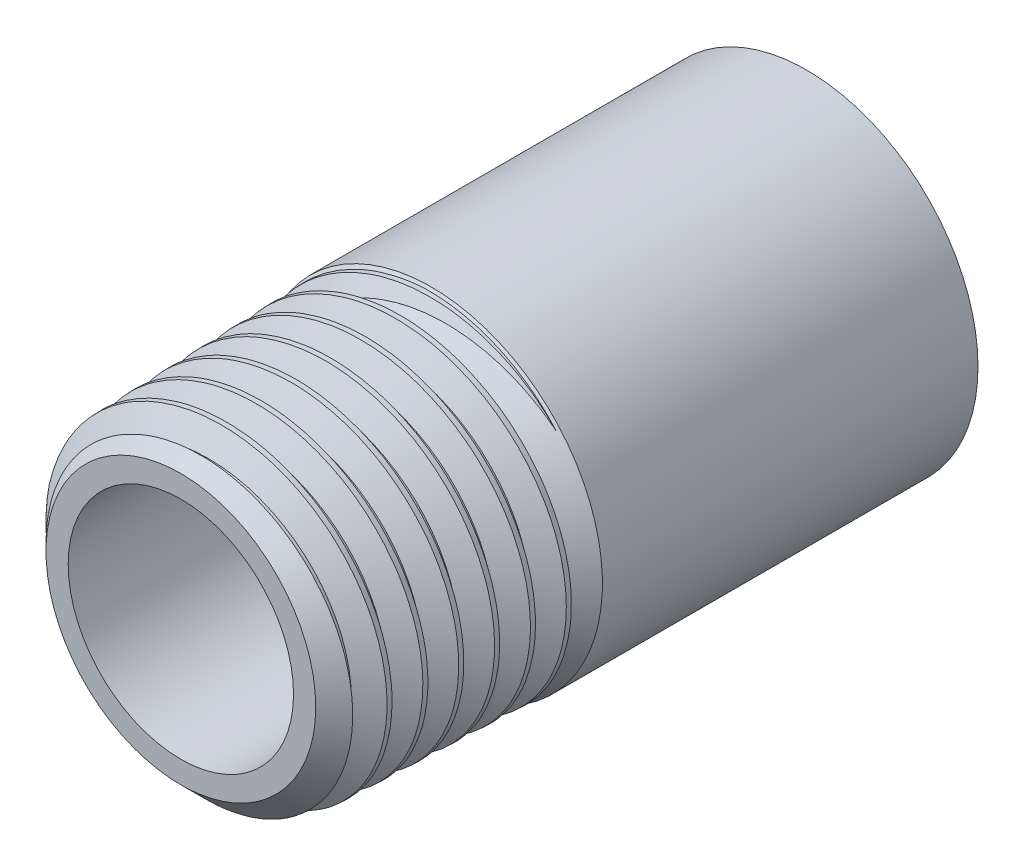
SolidWorks part; units mm, degrees
note: '?' marks a value the reader was unsure of.
ref_plane "Front" through (0, 0, 0) normal (0, 0, 1) x (1, 0, 0)
ref_plane "Top" through (0, 0, 0) normal (0, 1, 0) x (1, 0, 0)
ref_plane "Right" through (0, 0, 0) normal (1, 0, 0) x (0, 0, -1)
ref_axis "Axis1" through (0, 7.6398, 0) along (0, -1, 0)?
sketch "Layout" plane through (0, 0, 0) normal (1, 0, 0) x (0, 0, -1)
  line L0 (-12.7, 0) -> (12.7, 0) construction
  line L1 (-12.7, 4.572) -> (-12.7, 6.5417) construction
  line L2 (-12.7, 6.5417) -> (-2.54, 6.858) construction
  line L3 (-2.54, 6.858) -> (-2.54, 4.572) construction
  line L4 (-2.54, 4.572) -> (-12.7, 4.572) construction
  line L5 (0, 0) -> (0, 6.9453) construction
  point P9 (-2.54, 0)
  point P10 (-11.2889, 0)
  point P11 (2.54, 0)
  point P12 (11.2889, 0)
  dimension "D2" = 1.783
sketch "Sketch2" plane through (0, 0, 0) normal (1, 0, 0) x (0, 0, -1)
  line L0 (-12.7, 6.5417) -> (-2.54, 6.858) construction
  line L1 (-2.54, 6.858) -> (-2.54, 4.572) construction
  line L3 (-12.7, 4.572) -> (-12.7, 6.5417) construction
  line L4 (-12.7, 6.5417) -> (-2.54, 6.858)
  line L5 (-2.54, 6.858) -> (-2.54, 0)
  line L7 (-12.7, 0) -> (-12.7, 6.5417)
  line L8 (-12.7, 0) -> (-2.54, 0)
revolve "Revolve1" add sketch "Sketch2" angle 360 about L8
sketch "Sketch5" plane through (0, 0, 12.7) normal (0, 0, 1) x (1, 0, 0)
  circle A1 centre (0, 0) radius 6.5417
  circle A2 centre (0, 0) radius 6.5417 construction
curve "Helix/Spiral1"
sketch "Profile" plane through (0, 0, 0) normal (1, 0, 0) x (0, 0, -1)
  line L0 (-14.0229, 6.6944) -> (-12.6559, 6.618)
  line L1 (-12.6559, 6.618) -> (-13.2292, 5.6251)
  line L2 (-13.2292, 5.6251) -> (-13.4056, 5.6251)
  line L3 (-13.4056, 5.6251) -> (-14.0229, 6.6944)
  line L9 (-12.6118, 6.6944) -> (-14.0229, 6.6944) construction
  line L10 (-12.7, 6.5417) -> (-13.9347, 6.5417) construction
  line L11 (-13.3174, 6.618) -> (-12.6559, 6.618) construction
  line L12 (-13.3174, 6.5417) -> (-13.3174, 6.6944) construction
  line L13 (-14.0229, 6.6944) -> (-13.3174, 5.4724) construction
  line L14 (-13.3174, 5.4724) -> (-13.3174, 5.6251) construction
  line L15 (-13.3174, 5.4724) -> (-12.6118, 6.6944) construction
  line L16 (-13.2292, 5.6251) -> (-13.4056, 5.6251) construction
  line L17 (-13.3174, 6.618) -> (-13.9788, 6.618) construction
  dimension "D5" = 1.4111
  dimension "D6" = 0.1764
sketch "Sketch4" plane through (0, 0, 12.7) normal (0, 0, 1) x (1, 0, 0)
  circle A1 centre (0, 0) radius 5.4724
extrude "Cut-Extrude2" cut sketch "Sketch4" against normal through all draft 45 flip side to cut contours A1
sweep "Cut-Sweep1" cut profiles "Profile" path "Helix/Spiral1"
sketch "Sketch12" plane through (0, 0, 2.54) normal (0, 0, -1) x (-1, 0, 0)
  circle A0 centre (0, 0) radius 6.9453
extrude "Boss-Extrude1" add sketch "Sketch12" against normal through all draft 45
sketch "OD ref" plane through (0, 0, 0) normal (0, 0, 1) x (1, 0, 0)
  circle A1 centre (0, 0) radius 6.9453
  circle A2 centre (0, 0) radius 6.9453 construction
  dimension "D1" = 0
sketch "Sketch13" plane through (0, 0, 0) normal (0, 0, 1) x (1, 0, 0)
  circle A1 centre (0, 0) radius 6.9453
  circle A2 centre (0, 0) radius 6.9453
  dimension "D1" = 0
sketch "Sketch15" plane through (0, 0, 0) normal (0, 0, 1) x (1, 0, 0)
  circle A0 centre (0, 0) radius 4.572
extrude "Boss-Extrude2" add sketch "Sketch13" along normal up to vertex and the other way up to vertex (12.7 mm away) contours A2 up to point (0, 0, 2.54) other way up to point (0, 0, -12.7)
extrude "Cut-Extrude3" cut sketch "Sketch15" against normal through all both and the other way through all contours A0
sketch "Sketch16" plane through (0, 0, -12.7) normal (0, 0, -1) x (-1, 0, 0)
  circle A0 centre (0, 0) radius 6.9453
equation "\"D4@Helix/Spiral1\"=\"Pitch@Layout\""
equation "\"D3@Helix/Spiral1\"=\"ThreadEng@Layout\"+\"D4@Helix/Spiral1\""
equation "\"D6@Profile\"=\"D5@Profile\"*.125"
equation "\"D5@Profile\"=\"D4@Helix/Spiral1\""
